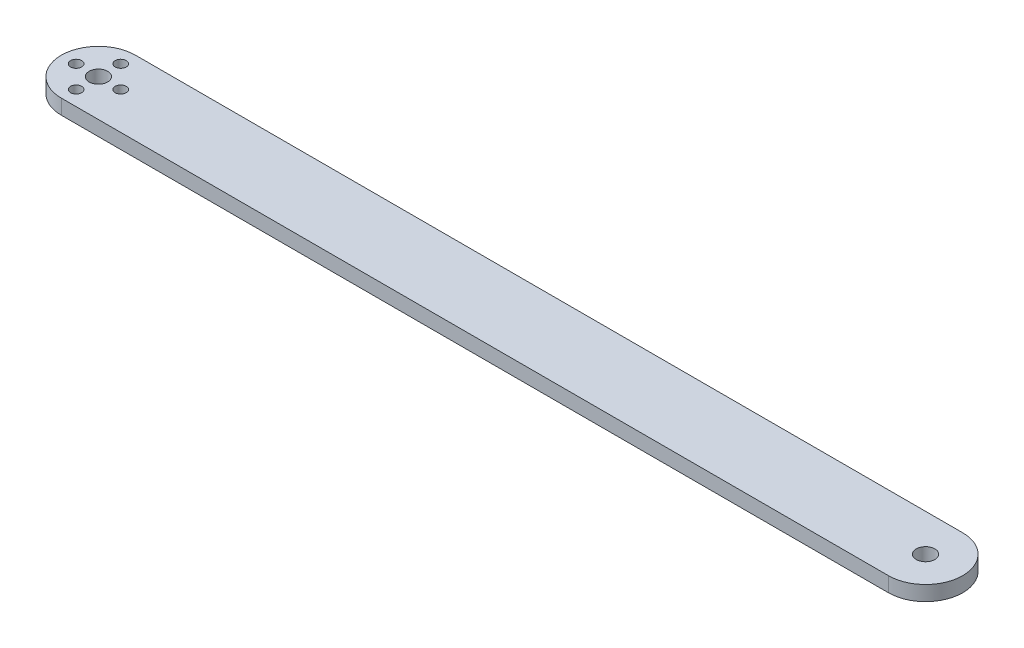
SolidWorks part; units mm, degrees
ref_plane "前视基准面" through (0, 0, 0) normal (0, 0, 1) x (1, 0, 0)
ref_plane "上视基准面" through (0, 0, 0) normal (0, 1, 0) x (1, 0, 0)
ref_plane "右视基准面" through (0, 0, 0) normal (1, 0, 0) x (0, 0, -1)
other "Configuration Table"
sketch "草图1" plane through (0, 0, 0) normal (0, 1, 0) x (1, 0, 0)
  line L0 (-111.375, 0) -> (111.375, 0) construction
  line L1 (-111.375, 10) -> (111.375, 10)
  line L2 (-111.375, -10) -> (111.375, -10)
  arc A0 (-111.375, 10) -> (-111.375, -10) centre (-111.375, 0) ccw
  arc A1 (111.375, -10) -> (111.375, 10) centre (111.375, 0) ccw
  circle A2 centre (-111.375, 0) radius 2.5
  circle A3 centre (111.375, 0) radius 2.5
  point P2 (0, 0)
  dimension "D2" = 10
  dimension "D3" = 5
  dimension "D4" = 5
  dimension "D1" = 222.75
extrude "凸台-拉伸1" add sketch "草图1" along normal blind 4
sketch "草图2" plane through (0, 4, 0) normal (0, 1, 0) x (1, 0, 0)
  circle A0 centre (-111.375, 6) radius 1.5
  circle A1 centre (-111.375, 0) radius 2.5 construction
  circle A2 centre (-111.375, 0) radius 2.5 construction
  point P5 (0, 0)
  dimension "D1" = 3
  dimension "D2" = 6
extrude "切除-拉伸1" cut sketch "草图2" against normal blind 4
pattern_circular "阵列(圆周)1" count 4 over 360 about axis through (-111.375, 4, 0) along (0, -1, 0) of "切除-拉伸1"
